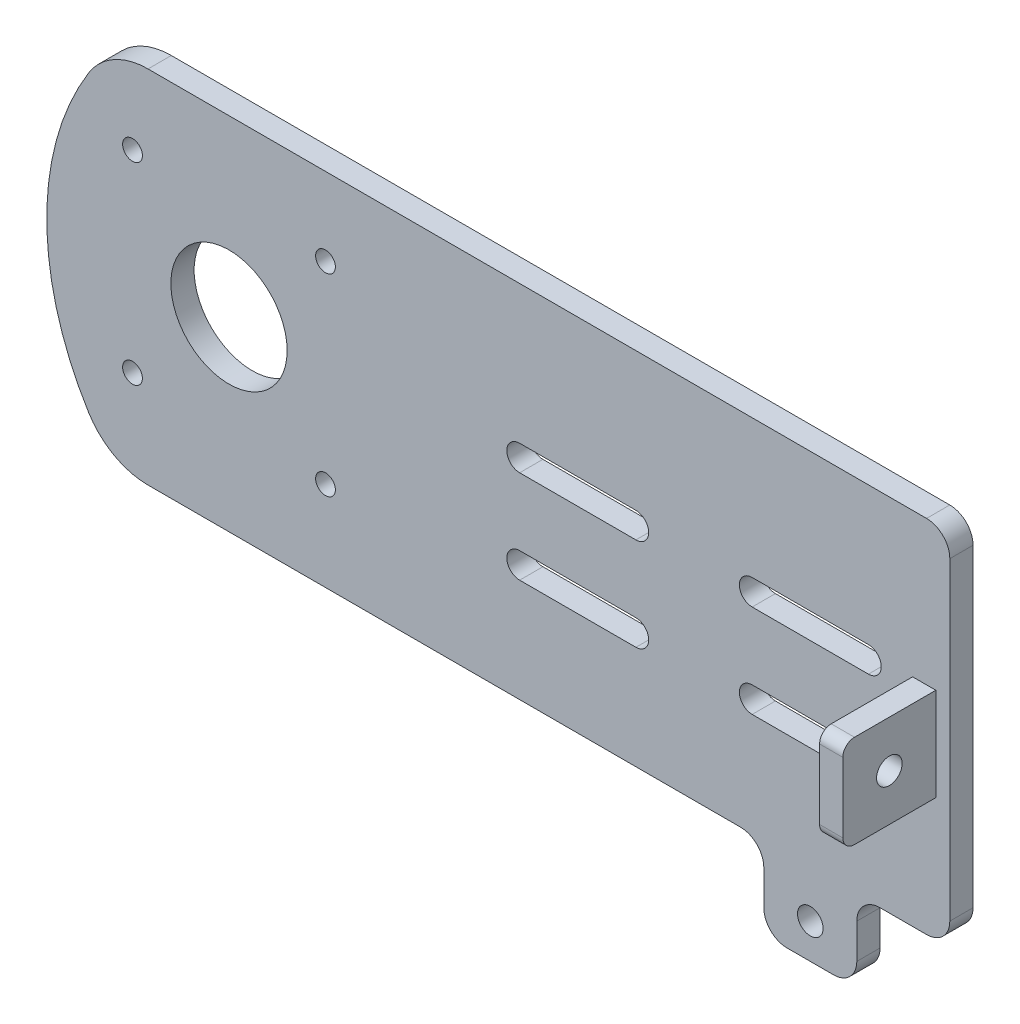
SolidWorks part; units mm, degrees
material "1.4003 (X2CrNi12)"
ref_plane "Ön Düzlem" through (0, 0, 0) normal (0, 0, 1) x (1, 0, 0)
ref_plane "Üst Düzlem" through (0, 0, 0) normal (0, 1, 0) x (1, 0, 0)
ref_plane "Sağ Düzlem" through (0, 0, 0) normal (1, 0, 0) x (0, 0, -1)
sketch "Çizim1" plane through (0, 0, 0) normal (0, 0, 1) x (1, 0, 0)
  line L4 (-360, 85) -> (-360, -70) construction
  line L5 (-360, -70) -> (-250, -70)
  line L6 (-250, -70) -> (-200, -70)
  line L7 (-200, -70) -> (-80, -70)
  line L8 (0, 0) -> (-360, 0) construction
  line L9 (-40, -70) -> (-40, -105)
  line L10 (-40, -105) -> (-80, -105)
  line L11 (-80, -105) -> (-80, -70)
  line L12 (-40, -70) -> (0, -70)
  line L13 (0, -70) -> (0, 0)
  line L14 (0, 0) -> (0, 85)
  line L15 (0, 85) -> (-360, 85)
  arc A0 (-360, 85) -> (-360, -70) centre (-268.3826, 7.5) ccw
  point P12 (-305, -70)
  dimension "D8" = 120
  dimension "D1" = 85
  dimension "D2" = 70
  dimension "D3" = 0
  dimension "D4" = 50
  dimension "D5" = 40
  dimension "D6" = 120
  dimension "D7" = 70
  dimension "D9" = 35
  dimension "D10" = 40
  dimension "D11" = 360
base flange "Taban-Flanş1" sketch "Çizim1" thickness 10 reverse thickness direction no parameters "D1"=2
sketch "Çizim2" plane through (0, 0, 0) normal (0, 0, 1) x (1, 0, 0)
  line L0 (0, 0) -> (-252.7239, 0) construction
  line L2 (-85, 20) -> (-35, 20) construction
  line L3 (-85, 25.5) -> (-35, 25.5)
  line L4 (-85, 14.5) -> (-35, 14.5)
  line L5 (-85, -20) -> (-35, -20) construction
  line L6 (-85, -14.5) -> (-35, -14.5)
  line L7 (-85, -25.5) -> (-35, -25.5)
  line L8 (-185, 20) -> (-135, 20) construction
  line L9 (-185, 25.5) -> (-135, 25.5)
  line L10 (-185, 14.5) -> (-135, 14.5)
  line L11 (-185, -20) -> (-135, -20) construction
  line L12 (-185, -14.5) -> (-135, -14.5)
  line L13 (-185, -25.5) -> (-135, -25.5)
  line L15 (-351.5, 51.5) -> (-268.5, 51.5) construction
  line L16 (-351.5, 51.5) -> (-351.5, -31.5) construction
  line L17 (-351.5, -31.5) -> (-268.5, -31.5) construction
  line L18 (-268.5, 51.5) -> (-268.5, -31.5) construction
  line L19 (-351.5, 51.5) -> (-268.5, -31.5) construction
  line L20 (-351.5, -31.5) -> (-268.5, 51.5) construction
  line L21 (0, -70) -> (0, 85) construction
  arc A0 (-85, 25.5) -> (-85, 14.5) centre (-85, 20) ccw
  arc A1 (-35, 14.5) -> (-35, 25.5) centre (-35, 20) ccw
  arc A2 (-85, -14.5) -> (-85, -25.5) centre (-85, -20) ccw
  arc A3 (-35, -25.5) -> (-35, -14.5) centre (-35, -20) ccw
  arc A4 (-185, 25.5) -> (-185, 14.5) centre (-185, 20) ccw
  arc A5 (-135, 14.5) -> (-135, 25.5) centre (-135, 20) ccw
  arc A6 (-185, -14.5) -> (-185, -25.5) centre (-185, -20) ccw
  arc A7 (-135, -25.5) -> (-135, -14.5) centre (-135, -20) ccw
  circle A8 centre (-310, 10) radius 25
  circle A9 centre (-351.5, 51.5) radius 4.25
  circle A10 centre (-268.5, 51.5) radius 4.25
  circle A11 centre (-351.5, -31.5) radius 4.25
  circle A12 centre (-268.5, -31.5) radius 4.25
  point P4 (-60, 20)
  point P11 (-60, -20)
  point P18 (-160, 20)
  point P25 (-160, -20)
  dimension "D1" = 5.5
  dimension "D2" = 5.5
  dimension "D3" = 5.5
  dimension "D4" = 5.5
  dimension "D13" = 50
  dimension "D18" = 8.5
  dimension "D11" = 310
  dimension "D5" = 50
  dimension "D6" = 50
  dimension "D7" = 50
  dimension "D8" = 50
  dimension "D9" = 20
  dimension "D10" = 20
  dimension "D12" = 100
  dimension "D14" = 10
  dimension "D16" = 83
  dimension "D17" = 83
extrude "Kes-Ekstrüzyon1" cut sketch "Çizim2" against normal blind 10
cosmetic thread "Kozmetik Diş Açma1"
cosmetic thread "Kozmetik Diş Açma2"
cosmetic thread "Kozmetik Diş Açma3"
cosmetic thread "Kozmetik Diş Açma4"
sketch "Çizim3" plane through (0, 0, 0) normal (0, 0, 1) x (1, 0, 0)
  line L0 (-80, -105) -> (-40, -105) construction
  line L1 (-40, -105) -> (-40, -70) construction
  circle A0 centre (-60, -90) radius 5.5
  dimension "D1" = 11
  dimension "D3" = 20
  dimension "D2" = 15
extrude "Kes-Ekstrüzyon2" cut sketch "Çizim3" against normal blind 20
sketch "Çizim4" plane through (0, 0, 0) normal (0, 0, 1) x (1, 0, 0)
  line L1 (-16, 23) -> (-6, 23)
  line L2 (-16, 23) -> (-16, -17)
  line L3 (-16, -17) -> (-6, -17)
  line L4 (-6, 23) -> (-6, -17)
  line L5 (-16, 23) -> (-6, -17) construction
  line L6 (-16, -17) -> (-6, 23) construction
  line L8 (0, -70) -> (0, 85) construction
  line L9 (-40, -70) -> (0, -70) construction
  point P0 (-11, 3)
  dimension "D1" = 10
  dimension "D2" = 40
  dimension "D3" = 6
  dimension "D4" = 73
extrude "Yükseklik-Ekstrüzyon1" add sketch "Çizim4" along normal blind 40 separate body
sketch "Çizim5" plane through (-6, 0, 0) normal (1, 0, 0) x (0, 0, -1)
  line L0 (-40, -17) -> (-40, 23) construction
  line L1 (-40, 23) -> (0, 23) construction
  circle A0 centre (-20, 3) radius 5.5
  dimension "D1" = 11
  dimension "D3" = 20
  dimension "D2" = 20
extrude "Kes-Ekstrüzyon3" cut sketch "Çizim5" against normal blind 40
fillet "Radyus3" radius 5 2 edges at (-11, -17, 40) (-11, 23, 40)
fillet "Radyus5" radius 10 4 edges at (-40, -70, -5) (-80, -70, -5) (-80, -105, -5) (-40, -105, -5)
fillet "Radyus6" radius 30 2 edges at (-360, 85, -5) (-360, -70, -5)
fillet "Radyus7" radius 10 2 edges at (0, -70, -5) (0, 85, -5)
sketch "Büküm-Çizgileri1" [suppressed] plane through (0, 0, 0) normal (0, 1, 0) x (1, 0, 0)
sketch "Sınırlandırma-Kutusu1" [suppressed] plane through (0, 0, 0) normal (0, 1, 0) x (1, 0, 0)
sheet metal parameters "Sac-Levha1" thickness 10 parameters "D1"=2
flat pattern "Düz-Çoğaltma1" [suppressed]
sketch "Büküm-Çizgileri2" plane through (0, 0, 0) normal (0, 1, 0) x (1, 0, 0)
sketch3d "Sınırlandırma-Kutusu2" [suppressed]
  line L0 (-120, -95, 0) -> (336.6856, -95, 0) construction
  line L1 (-120, 95, 0) -> (336.6856, 95, 0) construction
  line L2 (-120, -95, 0) -> (-120, 95, 0) construction
  line L3 (336.6856, -95, 0) -> (336.6856, 95, 0) construction
sheet metal parameters "Sac-Levha2" thickness 10 parameters "D1"=2
flat pattern "Düz-Çoğaltma1"
sketch "Büküm-Çizgileri2" plane through (0, 0, 0) normal (0, 1, 0) x (1, 0, 0)
sketch3d "Sınırlandırma-Kutusu2" [suppressed]
  line L0 (-113.9054, 89.6045, 0) -> (278.5268, 61.5736, 0) construction
  line L1 (-125.8343, -77.4006, 0) -> (266.5979, -105.4315, 0) construction
  line L2 (-113.9054, 89.6045, 0) -> (-125.8343, -77.4006, 0) construction
  line L3 (278.5268, 61.5736, 0) -> (266.5979, -105.4315, 0) construction
sheet metal parameters "Sac-Levha3" thickness 10 parameters "D1"=2
flat pattern "Düz-Çoğaltma1"
sketch "Büküm-Çizgileri2" plane through (0, 0, 0) normal (0, 1, 0) x (1, 0, 0)
sketch3d "Sınırlandırma-Kutusu2" [suppressed]
  line L0 (-120, -112.5, 0) -> (268.3826, -112.5, 0) construction
  line L1 (-120, 77.5, 0) -> (268.3826, 77.5, 0) construction
  line L2 (-120, -112.5, 0) -> (-120, 77.5, 0) construction
  line L3 (268.3826, -112.5, 0) -> (268.3826, 77.5, 0) construction
